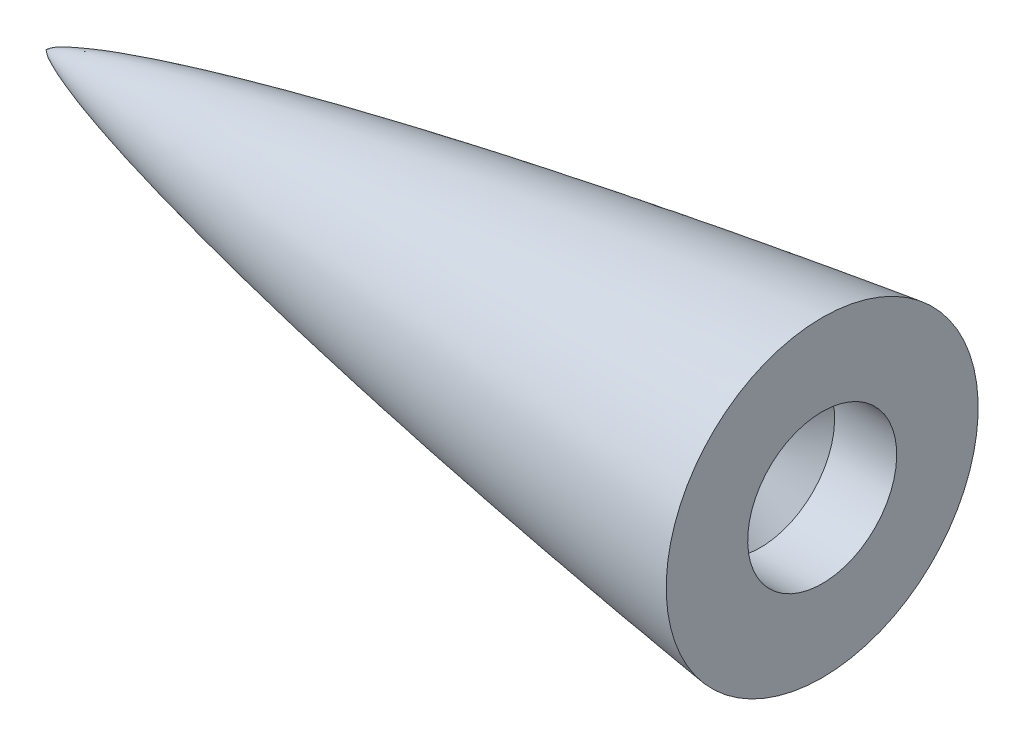
SolidWorks part; units mm, degrees
material "ABS"
ref_plane "Front Plane" through (0, 0, 0) normal (0, 0, 1) x (1, 0, 0)
ref_plane "Top Plane" through (0, 0, 0) normal (0, 1, 0) x (1, 0, 0)
ref_plane "Right Plane" through (0, 0, 0) normal (1, 0, 0) x (0, 0, -1)
curve "Curve1"
  spline degree 3 poles (0, 0, 0) (0.3238, 0.2558, 0) (0.9402, 0.7427, 0) (1.9959, 1.205, 0) (2.9891, 1.6586, 0) (3.9977, 2.0398, 0) (4.9964, 2.4132, 0) (5.9986, 2.7607, 0) (6.9987, 3.1004, 0) (7.9965, 3.4344, 0) (9.0008, 3.7373, 0) (9.9965, 4.055, 0) (11.0004, 4.3386, 0) (12, 4.6299, 0) (12.9986, 4.9215, 0) (13.9986, 5.202, 0) (15.0003, 5.4688, 0) (15.9984, 5.7426, 0) (17.0001, 5.9995, 0) (18.0001, 6.2594, 0) (18.9985, 6.5227, 0) (20.0004, 6.7686, 0) (20.9985, 7.0227, 0) (22.0002, 7.2591, 0) (22.9999, 7.5005, 0) (24.0003, 7.7389, 0) (24.9983, 7.9838, 0) (26.0019, 8.205, 0) (26.9969, 8.4568, 0) (28.0017, 8.6659, 0) (28.9999, 8.9005, 0) (29.9988, 9.1322, 0) (31.0001, 9.3496, 0) (32.0002, 9.5692, 0) (32.9985, 9.7935, 0) (34.0016, 9.9959, 0) (34.9985, 10.2236, 0) (36.0002, 10.4289, 0) (36.9999, 10.6405, 0) (38.0002, 10.8489, 0) (38.9986, 11.0636, 0) (40.0015, 11.2559, 0) (40.9986, 11.4736, 0) (42.0002, 11.6689, 0) (42.9999, 11.8705, 0) (44.0002, 12.0689, 0) (44.9986, 12.2737, 0) (46.0015, 12.4556, 0) (46.9985, 12.6646, 0) (48.0015, 12.8456, 0) (48.9986, 13.0537, 0) (50.0002, 13.2389, 0) (50.9999, 13.4305, 0) (52.0002, 13.619, 0) (52.9988, 13.8134, 0) (54.0012, 13.9868, 0) (55, 14.1802, 0) (55.9989, 14.3724, 0) (57.0001, 14.5493, 0) (58, 14.7302, 0) (59, 14.9099, 0) (60, 15.09, 0) (61, 15.2699, 0) (62, 15.4503, 0) (63.0002, 15.629, 0) (63.9988, 15.8137, 0) (65.0013, 15.9758, 0) (65.9988, 16.1637, 0) (67.0002, 16.329, 0) (68, 16.5003, 0) (69, 16.6699, 0) (70, 16.84, 0) (71, 17.01, 0) (72, 17.1799, 0) (73, 17.3503, 0) (74.0002, 17.519, 0) (74.9988, 17.6937, 0) (76.0012, 17.8458, 0) (76.9989, 18.0234, 0) (78, 18.1799, 0) (79.0011, 18.3368, 0) (79.9989, 18.5134, 0) (81.0002, 18.6691, 0) (82, 18.8303, 0) (83, 18.9899, 0) (84, 19.1503, 0) (85.0001, 19.3091, 0) (85.999, 19.4734, 0) (87.001, 19.6168, 0) (88, 19.78, 0) (88.999, 19.9434, 0) (90.0012, 20.0859, 0) (90.999, 20.2534, 0) (92, 20.4, 0) (93.001, 20.5468, 0) (93.999, 20.7134, 0) (95.0001, 20.8591, 0) (96, 21.0103, 0) (97, 21.1599, 0) (98, 21.3103, 0) (99.0001, 21.4591, 0) (99.999, 21.6134, 0) (101.001, 21.7468, 0) (102, 21.8999, 0) (102.999, 22.0535, 0) (104.0011, 22.1855, 0) (104.9988, 22.3446, 0) (106.0011, 22.4755, 0) (106.999, 22.6335, 0) (108, 22.7699, 0) (109.001, 22.9068, 0) (109.999, 23.0634, 0) (111.0001, 23.1991, 0) (112, 23.3402, 0) (113, 23.48, 0) (114, 23.62, 0) (115, 23.7602, 0) (116.0001, 23.8991, 0) (116.9991, 24.0435, 0) (118.0009, 24.1667, 0) (119, 24.3099, 0) (119.9991, 24.4535, 0) (121.0011, 24.5755, 0) (121.9989, 24.7247, 0) (123.0011, 24.8455, 0) (123.9991, 24.9935, 0) (125, 25.1199, 0) (126.0009, 25.2467, 0) (126.9991, 25.3935, 0) (128.0001, 25.5191, 0) (129, 25.6503, 0) (130, 25.7799, 0) (131, 25.91, 0) (132, 26.0399, 0) (133, 26.1703, 0) (134.0001, 26.2991, 0) (134.9991, 26.4335, 0) (136.0008, 26.5467, 0) (137, 26.6799, 0) (137.9991, 26.8136, 0) (139.001, 26.9255, 0) (139.999, 27.0647, 0) (141.001, 27.1755, 0) (141.9991, 27.3136, 0) (143, 27.4299, 0) (144.0008, 27.5467, 0) (144.9991, 27.6835, 0) (146.0001, 27.7991, 0) (147, 27.9203, 0) (148, 28.0399, 0) (149, 28.16, 0) (150, 28.28, 0) (151, 28.4, 0) (152, 28.52, 0) (153, 28.6399, 0) (154, 28.7603, 0) (155.0001, 28.879, 0) (155.9992, 29.0038, 0) (157.0009, 29.1054, 0) (157.9991, 29.2348, 0) (159.0009, 29.3351, 0) (159.9991, 29.4649, 0) (161.0009, 29.5651, 0) (161.9991, 29.6948, 0) (163.0009, 29.7954, 0) (163.9992, 29.9238, 0) (165.0001, 30.029, 0) (166, 30.1403, 0) (167, 30.2499, 0) (168, 30.36, 0) (169, 30.47, 0) (170, 30.58, 0) (171, 30.69, 0) (172, 30.8, 0) (173, 30.9099, 0) (174, 31.0203, 0) (175.0001, 31.129, 0) (175.9992, 31.2439, 0) (177.0008, 31.3354, 0) (177.9991, 31.4548, 0) (179.0009, 31.5451, 0) (179.9991, 31.6649, 0) (181.0009, 31.7551, 0) (181.9991, 31.8748, 0) (183.0008, 31.9654, 0) (183.9992, 32.0838, 0) (185.0001, 32.179, 0) (186, 32.28, 0) (186.9999, 32.3809, 0) (188.0007, 32.4765, 0) (188.9993, 32.5935, 0) (190.0001, 32.6893, 0) (191.0001, 32.7893, 0) (191.9993, 32.8935, 0) (193.0007, 32.9764, 0) (193.9999, 33.0812, 0) (195.0001, 33.1788, 0) (195.9993, 33.2836, 0) (197.0006, 33.3667, 0) (198, 33.4699, 0) (198.9993, 33.5736, 0) (200.0007, 33.6554, 0) (200.9992, 33.7648, 0) (202.0008, 33.8454, 0) (202.9993, 33.9539, 0) (204.0001, 34.0387, 0) (204.9999, 34.1313, 0) (206.0007, 34.2163, 0) (206.9993, 34.3236, 0) (208.0001, 34.409, 0) (209, 34.5003, 0) (210, 34.5899, 0) (211, 34.6803, 0) (212.0001, 34.769, 0) (212.9994, 34.8635, 0) (214.0006, 34.9366, 0) (215, 35.03, 0) (215.9994, 35.1233, 0) (217.0006, 35.1967, 0) (218, 35.2899, 0) (218.9994, 35.3835, 0) (220.0006, 35.4558, 0) (220.9994, 35.5535, 0) (222, 35.6299, 0) (223.0006, 35.7067, 0) (223.9994, 35.8035, 0) (225.0001, 35.879, 0) (226, 35.9603, 0) (227, 36.0399, 0) (228, 36.12, 0) (229, 36.2, 0) (230, 36.2799, 0) (231, 36.3603, 0) (232.0001, 36.439, 0) (232.9995, 36.5235, 0) (234.0005, 36.5867, 0) (235, 36.6699, 0) (235.9995, 36.7535, 0) (237.0006, 36.8157, 0) (237.9995, 36.9035, 0) (239, 36.9699, 0) (240.0005, 37.0367, 0) (240.9995, 37.1235, 0) (242.0001, 37.189, 0) (243, 37.2603, 0) (244, 37.3299, 0) (245, 37.4, 0) (246, 37.47, 0) (247, 37.5399, 0) (248, 37.6103, 0) (249.0001, 37.6789, 0) (249.9995, 37.7539, 0) (251.0005, 37.8053, 0) (251.9995, 37.8849, 0) (253.0005, 37.9351, 0) (253.9995, 38.0149, 0) (255.0005, 38.0653, 0) (255.9995, 38.1439, 0) (257.0001, 38.1989, 0) (258, 38.2603, 0) (259, 38.3199, 0) (260, 38.38, 0) (261, 38.4399, 0) (262, 38.5003, 0) (263.0001, 38.5589, 0) (263.9996, 38.6239, 0) (265.0004, 38.6653, 0) (265.9995, 38.7349, 0) (267.0005, 38.7751, 0) (267.9995, 38.8449, 0) (269.0004, 38.8853, 0) (269.9996, 38.9539, 0) (271.0001, 38.999, 0) (272, 39.0502, 0) (273, 39.1002, 0) (274, 39.1491, 0) (274.9997, 39.2036, 0) (276.0003, 39.2365, 0) (277, 39.2903, 0) (277.9997, 39.3424, 0) (279, 39.3803, 0) (280.0003, 39.4166, 0) (280.9997, 39.4735, 0) (282, 39.5093, 0) (283, 39.5493, 0) (283.9998, 39.5935, 0) (285.0002, 39.6166, 0) (286, 39.6602, 0) (286.9998, 39.7026, 0) (288, 39.7293, 0) (289, 39.7602, 0) (290, 39.7899, 0) (291, 39.8203, 0) (292, 39.849, 0) (292.9998, 39.8839, 0) (294.0002, 39.8955, 0) (294.9998, 39.9341, 0) (296, 39.9482, 0) (296.9999, 39.9732, 0) (298, 39.9792, 0) (299, 39.9902, 0) (299.6667, 39.9967, 0) (300, 40, 0) knots 0 0 0 0 0.004059 0.007728 0.011327 0.014863 0.018375 0.021865 0.025345 0.028814 0.032263 0.035712 0.039142 0.042572 0.046002 0.049423 0.052835 0.056247 0.059651 0.063054 0.066458 0.069854 0.07325 0.076637 0.080025 0.083413 0.086801 0.090181 0.093569 0.096942 0.100322 0.103702 0.107075 0.110448 0.113821 0.117187 0.120561 0.123927 0.127293 0.130659 0.134025 0.137384 0.140751 0.14411 0.147469 0.150829 0.154188 0.157542 0.160901 0.164254 0.167614 0.170967 0.17432 0.177673 0.181027 0.184374 0.187727 0.19108 0.194427 0.197774 0.201122 0.204469 0.207816 0.211163 0.21451 0.217858 0.221199 0.224546 0.227888 0.231229 0.234571 0.237912 0.241254 0.244595 0.247937 0.251278 0.25462 0.257956 0.261298 0.264634 0.26797 0.271311 0.274648 0.277984 0.28132 0.284656 0.287992 0.291328 0.294659 0.297995 0.301332 0.304663 0.307999 0.31133 0.314661 0.317997 0.321328 0.324659 0.327991 0.331322 0.334653 0.337984 0.34131 0.344641 0.347972 0.351299 0.35463 0.357956 0.361287 0.364614 0.36794 0.371271 0.374598 0.377924 0.38125 0.384577 0.387903 0.391229 0.394556 0.397878 0.401204 0.404531 0.407853 0.411179 0.414501 0.417827 0.421149 0.424471 0.427798 0.43112 0.434442 0.437763 0.441085 0.444407 0.447729 0.451051 0.454373 0.457691 0.461013 0.464335 0.467653 0.470975 0.474293 0.477615 0.480933 0.484251 0.487573 0.49089 0.494208 0.497526 0.500844 0.504162 0.50748 0.510798 0.514116 0.517434 0.520751 0.524069 0.527383 0.530701 0.534015 0.537333 0.540647 0.543965 0.547279 0.550597 0.553911 0.557226 0.56054 0.563854 0.567168 0.570482 0.573796 0.57711 0.580424 0.583738 0.587053 0.590367 0.593677 0.596991 0.600302 0.603616 0.606927 0.610241 0.613552 0.616866 0.620177 0.623487 0.626798 0.630109 0.633423 0.636733 0.640044 0.643355 0.646662 0.649973 0.653284 0.656594 0.659902 0.663213 0.666523 0.669831 0.673142 0.676449 0.67976 0.683067 0.686375 0.689682 0.692993 0.696301 0.699608 0.702916 0.706223 0.709531 0.712838 0.716143 0.719451 0.722758 0.726063 0.729371 0.732678 0.735983 0.739291 0.742595 0.7459 0.749208 0.752513 0.755817 0.759122 0.762427 0.765732 0.769036 0.772341 0.775646 0.778951 0.782253 0.785558 0.788863 0.792165 0.79547 0.798772 0.802074 0.805379 0.808681 0.811984 0.815286 0.818588 0.821891 0.825193 0.828495 0.831797 0.8351 0.8384 0.841702 0.845002 0.848305 0.851605 0.854907 0.858207 0.861508 0.864808 0.868108 0.871408 0.874708 0.878008 0.881309 0.884607 0.887907 0.891206 0.894506 0.897804 0.901104 0.904403 0.907701 0.910999 0.914298 0.917596 0.920893 0.924191 0.92749 0.930787 0.934083 0.937382 0.940679 0.943976 0.947272 0.950568 0.953865 0.957162 0.960458 0.963753 0.967049 0.970345 0.973641 0.976936 0.980231 0.983527 0.986822 0.990117 0.993411 0.996706 1 1 1 1
sketch "Sketch1" plane through (0, 0, 0) normal (0, 0, 1) x (1, 0, 0)
  line L0 (125, 25.12) -> (125, 3.175)
  line L1 (21.825, 0) -> (0, 0)
  line L2 (1366, 0) -> (125, 0) construction
  line L3 (125, 3.175) -> (25, 3.175)
  line L4 (25, 3.175) -> (21.825, 0)
  line L5 (21.825, 0) -> (-59.4496, 0) construction
  line L6 (125, 12) -> (115, 12)
  line L7 (115, 12) -> (106.175, 3.175)
  spline S0 degree 3 poles (-1070.3353, 1688.9679) (10.2744, -68.4827) (-11.5783, -4.7393) (1.9959, 1.205) (2.9891, 1.6586) (3.9977, 2.0398) (4.9964, 2.4132) (5.9986, 2.7607) (6.9987, 3.1004) (7.9965, 3.4344) (9.0008, 3.7373) (9.9965, 4.055) (11.0004, 4.3386) (12, 4.6299) (12.9986, 4.9215) (13.9986, 5.202) (15.0003, 5.4688) (15.9984, 5.7426) (17.0001, 5.9995) (18.0001, 6.2594) (18.9985, 6.5227) (20.0004, 6.7686) (20.9985, 7.0227) (22.0002, 7.2591) (22.9999, 7.5005) (24.0003, 7.7389) (24.9983, 7.9838) (26.0019, 8.205) (26.9969, 8.4568) (28.0017, 8.6659) (28.9999, 8.9005) (29.9988, 9.1322) (31.0001, 9.3496) (32.0002, 9.5692) (32.9985, 9.7935) (34.0016, 9.9959) (34.9985, 10.2236) (36.0002, 10.4289) (36.9999, 10.6405) (38.0002, 10.8489) (38.9986, 11.0636) (40.0015, 11.2559) (40.9986, 11.4736) (42.0002, 11.6689) (42.9999, 11.8705) (44.0002, 12.0689) (44.9986, 12.2737) (46.0015, 12.4556) (46.9985, 12.6646) (48.0015, 12.8456) (48.9986, 13.0537) (50.0002, 13.2389) (50.9999, 13.4305) (52.0002, 13.619) (52.9988, 13.8134) (54.0012, 13.9868) (55, 14.1802) (55.9989, 14.3724) (57.0001, 14.5493) (58, 14.7302) (59, 14.9099) (60, 15.09) (61, 15.2699) (62, 15.4503) (63.0002, 15.629) (63.9988, 15.8137) (65.0013, 15.9758) (65.9988, 16.1637) (67.0002, 16.329) (68, 16.5003) (69, 16.6699) (70, 16.84) (71, 17.01) (72, 17.1799) (73, 17.3503) (74.0002, 17.519) (74.9988, 17.6937) (76.0012, 17.8458) (76.9989, 18.0234) (78, 18.1799) (79.0011, 18.3368) (79.9989, 18.5134) (81.0002, 18.6691) (82, 18.8303) (83, 18.9899) (84, 19.1503) (85.0001, 19.3091) (85.999, 19.4734) (87.001, 19.6168) (88, 19.78) (88.999, 19.9434) (90.0012, 20.0859) (90.999, 20.2534) (92, 20.4) (93.001, 20.5468) (93.999, 20.7134) (95.0001, 20.8591) (96, 21.0103) (97, 21.1599) (98, 21.3103) (99.0001, 21.4591) (99.999, 21.6134) (101.001, 21.7468) (102, 21.8999) (102.999, 22.0535) (104.0011, 22.1855) (104.9988, 22.3446) (106.0011, 22.4755) (106.999, 22.6335) (108, 22.7699) (109.001, 22.9068) (109.999, 23.0634) (111.0001, 23.1991) (112, 23.3402) (113, 23.48) (114, 23.62) (115, 23.7602) (116.0001, 23.8991) (116.9991, 24.0435) (118.0009, 24.1667) (119, 24.3099) (119.9991, 24.4535) (121.0011, 24.5755) (121.9989, 24.7247) (123.0011, 24.8455) (123.9991, 24.9935) (125, 25.1199) (126.0009, 25.2467) (126.9991, 25.3935) (128.0001, 25.5191) (129, 25.6503) (130, 25.7799) (131, 25.91) (132, 26.0399) (133, 26.1703) (134.0001, 26.2991) (134.9991, 26.4335) (136.0008, 26.5467) (137, 26.6799) (137.9991, 26.8136) (139.001, 26.9255) (139.999, 27.0647) (141.001, 27.1755) (141.9991, 27.3136) (143, 27.4299) (144.0008, 27.5467) (144.9991, 27.6835) (146.0001, 27.7991) (147, 27.9203) (148, 28.0399) (149, 28.16) (150, 28.28) (151, 28.4) (152, 28.52) (153, 28.6399) (154, 28.7603) (155.0001, 28.879) (155.9992, 29.0038) (157.0009, 29.1054) (157.9991, 29.2348) (159.0009, 29.3351) (159.9991, 29.4649) (161.0009, 29.5651) (161.9991, 29.6948) (163.0009, 29.7954) (163.9992, 29.9238) (165.0001, 30.029) (166, 30.1403) (167, 30.2499) (168, 30.36) (169, 30.47) (170, 30.58) (171, 30.69) (172, 30.8) (173, 30.9099) (174, 31.0203) (175.0001, 31.129) (175.9992, 31.2439) (177.0008, 31.3354) (177.9991, 31.4548) (179.0009, 31.5451) (179.9991, 31.6649) (181.0009, 31.7551) (181.9991, 31.8748) (183.0008, 31.9654) (183.9992, 32.0838) (185.0001, 32.179) (186, 32.28) (186.9999, 32.3809) (188.0007, 32.4765) (188.9993, 32.5935) (190.0001, 32.6893) (191.0001, 32.7893) (191.9993, 32.8935) (193.0007, 32.9764) (193.9999, 33.0812) (195.0001, 33.1788) (195.9993, 33.2836) (197.0006, 33.3667) (198, 33.4699) (198.9993, 33.5736) (200.0007, 33.6554) (200.9992, 33.7648) (202.0008, 33.8454) (202.9993, 33.9539) (204.0001, 34.0387) (204.9999, 34.1313) (206.0007, 34.2163) (206.9993, 34.3236) (208.0001, 34.409) (209, 34.5003) (210, 34.5899) (211, 34.6803) (212.0001, 34.769) (212.9994, 34.8635) (214.0006, 34.9366) (215, 35.03) (215.9994, 35.1233) (217.0006, 35.1967) (218, 35.2899) (218.9994, 35.3835) (220.0006, 35.4558) (220.9994, 35.5535) (222, 35.6299) (223.0006, 35.7067) (223.9994, 35.8035) (225.0001, 35.879) (226, 35.9603) (227, 36.0399) (228, 36.12) (229, 36.2) (230, 36.2799) (231, 36.3603) (232.0001, 36.439) (232.9995, 36.5235) (234.0005, 36.5867) (235, 36.6699) (235.9995, 36.7535) (237.0006, 36.8157) (237.9995, 36.9035) (239, 36.9699) (240.0005, 37.0367) (240.9995, 37.1235) (242.0001, 37.189) (243, 37.2603) (244, 37.3299) (245, 37.4) (246, 37.47) (247, 37.5399) (248, 37.6103) (249.0001, 37.6789) (249.9995, 37.7539) (251.0005, 37.8053) (251.9995, 37.8849) (253.0005, 37.9351) (253.9995, 38.0149) (255.0005, 38.0653) (255.9995, 38.1439) (257.0001, 38.1989) (258, 38.2603) (259, 38.3199) (260, 38.38) (261, 38.4399) (262, 38.5003) (263.0001, 38.5589) (263.9996, 38.6239) (265.0004, 38.6653) (265.9995, 38.7349) (267.0005, 38.7751) (267.9995, 38.8449) (269.0004, 38.8853) (269.9996, 38.9539) (271.0001, 38.999) (272, 39.0502) (273, 39.1002) (274, 39.1491) (274.9997, 39.2036) (276.0003, 39.2365) (277, 39.2903) (277.9997, 39.3424) (279, 39.3803) (280.0003, 39.4166) (280.9997, 39.4735) (282, 39.5093) (283, 39.5493) (283.9998, 39.5935) (285.0002, 39.6166) (286, 39.6602) (286.9998, 39.7026) (288, 39.7293) (289, 39.7602) (290, 39.7899) (291, 39.8203) (292, 39.849) (292.9998, 39.8839) (294.0002, 39.8955) (294.9998, 39.9341) (296, 39.9482) (296.9999, 39.9732) (298, 39.9792) (369.4003, 40.7684) (440.6193, 31.9722) (479.6754, 2027.9914) knots -0.134313 -0.134313 -0.134313 -0.134313 0.004059 0.007728 0.011327 0.014863 0.018375 0.021865 0.025345 0.028814 0.032263 0.035712 0.039142 0.042572 0.046002 0.049423 0.052835 0.056247 0.059651 0.063054 0.066458 0.069854 0.07325 0.076637 0.080025 0.083413 0.086801 0.090181 0.093569 0.096942 0.100322 0.103702 0.107075 0.110448 0.113821 0.117187 0.120561 0.123927 0.127293 0.130659 0.134025 0.137384 0.140751 0.14411 0.147469 0.150829 0.154188 0.157542 0.160901 0.164254 0.167614 0.170967 0.17432 0.177673 0.181027 0.184374 0.187727 0.19108 0.194427 0.197774 0.201122 0.204469 0.207816 0.211163 0.21451 0.217858 0.221199 0.224546 0.227888 0.231229 0.234571 0.237912 0.241254 0.244595 0.247937 0.251278 0.25462 0.257956 0.261298 0.264634 0.26797 0.271311 0.274648 0.277984 0.28132 0.284656 0.287992 0.291328 0.294659 0.297995 0.301332 0.304663 0.307999 0.31133 0.314661 0.317997 0.321328 0.324659 0.327991 0.331322 0.334653 0.337984 0.34131 0.344641 0.347972 0.351299 0.35463 0.357956 0.361287 0.364614 0.36794 0.371271 0.374598 0.377924 0.38125 0.384577 0.387903 0.391229 0.394556 0.397878 0.401204 0.404531 0.407853 0.411179 0.414501 0.417827 0.421149 0.424471 0.427798 0.43112 0.434442 0.437763 0.441085 0.444407 0.447729 0.451051 0.454373 0.457691 0.461013 0.464335 0.467653 0.470975 0.474293 0.477615 0.480933 0.484251 0.487573 0.49089 0.494208 0.497526 0.500844 0.504162 0.50748 0.510798 0.514116 0.517434 0.520751 0.524069 0.527383 0.530701 0.534015 0.537333 0.540647 0.543965 0.547279 0.550597 0.553911 0.557226 0.56054 0.563854 0.567168 0.570482 0.573796 0.57711 0.580424 0.583738 0.587053 0.590367 0.593677 0.596991 0.600302 0.603616 0.606927 0.610241 0.613552 0.616866 0.620177 0.623487 0.626798 0.630109 0.633423 0.636733 0.640044 0.643355 0.646662 0.649973 0.653284 0.656594 0.659902 0.663213 0.666523 0.669831 0.673142 0.676449 0.67976 0.683067 0.686375 0.689682 0.692993 0.696301 0.699608 0.702916 0.706223 0.709531 0.712838 0.716143 0.719451 0.722758 0.726063 0.729371 0.732678 0.735983 0.739291 0.742595 0.7459 0.749208 0.752513 0.755817 0.759122 0.762427 0.765732 0.769036 0.772341 0.775646 0.778951 0.782253 0.785558 0.788863 0.792165 0.79547 0.798772 0.802074 0.805379 0.808681 0.811984 0.815286 0.818588 0.821891 0.825193 0.828495 0.831797 0.8351 0.8384 0.841702 0.845002 0.848305 0.851605 0.854907 0.858207 0.861508 0.864808 0.868108 0.871408 0.874708 0.878008 0.881309 0.884607 0.887907 0.891206 0.894506 0.897804 0.901104 0.904403 0.907701 0.910999 0.914298 0.917596 0.920893 0.924191 0.92749 0.930787 0.934083 0.937382 0.940679 0.943976 0.947272 0.950568 0.953865 0.957162 0.960458 0.963753 0.967049 0.970345 0.973641 0.976936 0.980231 0.983527 0.986822 0.990117 0.993411 0.996706 1.695794 1.695794 1.695794 1.695794 only from (0, 0) to (300, 40) construction
  spline S1 degree 3 poles (0, 0) (0.3238, 0.2558) (0.9402, 0.7427) (1.9959, 1.205) (2.9891, 1.6586) (3.9977, 2.0398) (4.9964, 2.4132) (5.9986, 2.7607) (6.9987, 3.1004) (7.9965, 3.4344) (9.0008, 3.7373) (9.9965, 4.055) (11.0004, 4.3386) (12, 4.6299) (12.9986, 4.9215) (13.9986, 5.202) (15.0003, 5.4688) (15.9984, 5.7426) (17.0001, 5.9995) (18.0001, 6.2594) (18.9985, 6.5227) (20.0004, 6.7686) (20.9985, 7.0227) (22.0002, 7.2591) (22.9999, 7.5005) (24.0003, 7.7389) (24.9983, 7.9838) (26.0019, 8.205) (26.9969, 8.4568) (28.0017, 8.6659) (28.9999, 8.9005) (29.9988, 9.1322) (31.0001, 9.3496) (32.0002, 9.5692) (32.9985, 9.7935) (34.0016, 9.9959) (34.9985, 10.2236) (36.0002, 10.4289) (36.9999, 10.6405) (38.0002, 10.8489) (38.9986, 11.0636) (40.0015, 11.2559) (40.9986, 11.4736) (42.0002, 11.6689) (42.9999, 11.8705) (44.0002, 12.0689) (44.9986, 12.2737) (46.0015, 12.4556) (46.9985, 12.6646) (48.0015, 12.8456) (48.9986, 13.0537) (50.0002, 13.2389) (50.9999, 13.4305) (52.0002, 13.619) (52.9988, 13.8134) (54.0012, 13.9868) (55, 14.1802) (55.9989, 14.3724) (57.0001, 14.5493) (58, 14.7302) (59, 14.9099) (60, 15.09) (61, 15.2699) (62, 15.4503) (63.0002, 15.629) (63.9988, 15.8137) (65.0013, 15.9758) (65.9988, 16.1637) (67.0002, 16.329) (68, 16.5003) (69, 16.6699) (70, 16.84) (71, 17.01) (72, 17.1799) (73, 17.3503) (74.0002, 17.519) (74.9988, 17.6937) (76.0012, 17.8458) (76.9989, 18.0234) (78, 18.1799) (79.0011, 18.3368) (79.9989, 18.5134) (81.0002, 18.6691) (82, 18.8303) (83, 18.9899) (84, 19.1503) (85.0001, 19.3091) (85.999, 19.4734) (87.001, 19.6168) (88, 19.78) (88.999, 19.9434) (90.0012, 20.0859) (90.999, 20.2534) (92, 20.4) (93.001, 20.5468) (93.999, 20.7134) (95.0001, 20.8591) (96, 21.0103) (97, 21.1599) (98, 21.3103) (99.0001, 21.4591) (99.999, 21.6134) (101.001, 21.7468) (102, 21.8999) (102.999, 22.0535) (104.0011, 22.1855) (104.9988, 22.3446) (106.0011, 22.4755) (106.999, 22.6335) (108, 22.7699) (109.001, 22.9068) (109.999, 23.0634) (111.0001, 23.1991) (112, 23.3402) (113, 23.48) (114, 23.62) (115, 23.7602) (116.0001, 23.8991) (116.9991, 24.0435) (118.0009, 24.1667) (119, 24.3099) (119.9991, 24.4535) (121.0011, 24.5755) (121.9989, 24.7247) (123.0011, 24.8455) (123.9991, 24.9935) (125, 25.1199) (126.0009, 25.2467) (126.9991, 25.3935) (128.0001, 25.5191) (129, 25.6503) (130, 25.7799) (131, 25.91) (132, 26.0399) (133, 26.1703) (134.0001, 26.2991) (134.9991, 26.4335) (136.0008, 26.5467) (137, 26.6799) (137.9991, 26.8136) (139.001, 26.9255) (139.999, 27.0647) (141.001, 27.1755) (141.9991, 27.3136) (143, 27.4299) (144.0008, 27.5467) (144.9991, 27.6835) (146.0001, 27.7991) (147, 27.9203) (148, 28.0399) (149, 28.16) (150, 28.28) (151, 28.4) (152, 28.52) (153, 28.6399) (154, 28.7603) (155.0001, 28.879) (155.9992, 29.0038) (157.0009, 29.1054) (157.9991, 29.2348) (159.0009, 29.3351) (159.9991, 29.4649) (161.0009, 29.5651) (161.9991, 29.6948) (163.0009, 29.7954) (163.9992, 29.9238) (165.0001, 30.029) (166, 30.1403) (167, 30.2499) (168, 30.36) (169, 30.47) (170, 30.58) (171, 30.69) (172, 30.8) (173, 30.9099) (174, 31.0203) (175.0001, 31.129) (175.9992, 31.2439) (177.0008, 31.3354) (177.9991, 31.4548) (179.0009, 31.5451) (179.9991, 31.6649) (181.0009, 31.7551) (181.9991, 31.8748) (183.0008, 31.9654) (183.9992, 32.0838) (185.0001, 32.179) (186, 32.28) (186.9999, 32.3809) (188.0007, 32.4765) (188.9993, 32.5935) (190.0001, 32.6893) (191.0001, 32.7893) (191.9993, 32.8935) (193.0007, 32.9764) (193.9999, 33.0812) (195.0001, 33.1788) (195.9993, 33.2836) (197.0006, 33.3667) (198, 33.4699) (198.9993, 33.5736) (200.0007, 33.6554) (200.9992, 33.7648) (202.0008, 33.8454) (202.9993, 33.9539) (204.0001, 34.0387) (204.9999, 34.1313) (206.0007, 34.2163) (206.9993, 34.3236) (208.0001, 34.409) (209, 34.5003) (210, 34.5899) (211, 34.6803) (212.0001, 34.769) (212.9994, 34.8635) (214.0006, 34.9366) (215, 35.03) (215.9994, 35.1233) (217.0006, 35.1967) (218, 35.2899) (218.9994, 35.3835) (220.0006, 35.4558) (220.9994, 35.5535) (222, 35.6299) (223.0006, 35.7067) (223.9994, 35.8035) (225.0001, 35.879) (226, 35.9603) (227, 36.0399) (228, 36.12) (229, 36.2) (230, 36.2799) (231, 36.3603) (232.0001, 36.439) (232.9995, 36.5235) (234.0005, 36.5867) (235, 36.6699) (235.9995, 36.7535) (237.0006, 36.8157) (237.9995, 36.9035) (239, 36.9699) (240.0005, 37.0367) (240.9995, 37.1235) (242.0001, 37.189) (243, 37.2603) (244, 37.3299) (245, 37.4) (246, 37.47) (247, 37.5399) (248, 37.6103) (249.0001, 37.6789) (249.9995, 37.7539) (251.0005, 37.8053) (251.9995, 37.8849) (253.0005, 37.9351) (253.9995, 38.0149) (255.0005, 38.0653) (255.9995, 38.1439) (257.0001, 38.1989) (258, 38.2603) (259, 38.3199) (260, 38.38) (261, 38.4399) (262, 38.5003) (263.0001, 38.5589) (263.9996, 38.6239) (265.0004, 38.6653) (265.9995, 38.7349) (267.0005, 38.7751) (267.9995, 38.8449) (269.0004, 38.8853) (269.9996, 38.9539) (271.0001, 38.999) (272, 39.0502) (273, 39.1002) (274, 39.1491) (274.9997, 39.2036) (276.0003, 39.2365) (277, 39.2903) (277.9997, 39.3424) (279, 39.3803) (280.0003, 39.4166) (280.9997, 39.4735) (282, 39.5093) (283, 39.5493) (283.9998, 39.5935) (285.0002, 39.6166) (286, 39.6602) (286.9998, 39.7026) (288, 39.7293) (289, 39.7602) (290, 39.7899) (291, 39.8203) (292, 39.849) (292.9998, 39.8839) (294.0002, 39.8955) (294.9998, 39.9341) (296, 39.9482) (296.9999, 39.9732) (298, 39.9792) (299, 39.9902) (299.6667, 39.9967) (300, 40) knots 0 0 0 0 0.004059 0.007728 0.011327 0.014863 0.018375 0.021865 0.025345 0.028814 0.032263 0.035712 0.039142 0.042572 0.046002 0.049423 0.052835 0.056247 0.059651 0.063054 0.066458 0.069854 0.07325 0.076637 0.080025 0.083413 0.086801 0.090181 0.093569 0.096942 0.100322 0.103702 0.107075 0.110448 0.113821 0.117187 0.120561 0.123927 0.127293 0.130659 0.134025 0.137384 0.140751 0.14411 0.147469 0.150829 0.154188 0.157542 0.160901 0.164254 0.167614 0.170967 0.17432 0.177673 0.181027 0.184374 0.187727 0.19108 0.194427 0.197774 0.201122 0.204469 0.207816 0.211163 0.21451 0.217858 0.221199 0.224546 0.227888 0.231229 0.234571 0.237912 0.241254 0.244595 0.247937 0.251278 0.25462 0.257956 0.261298 0.264634 0.26797 0.271311 0.274648 0.277984 0.28132 0.284656 0.287992 0.291328 0.294659 0.297995 0.301332 0.304663 0.307999 0.31133 0.314661 0.317997 0.321328 0.324659 0.327991 0.331322 0.334653 0.337984 0.34131 0.344641 0.347972 0.351299 0.35463 0.357956 0.361287 0.364614 0.36794 0.371271 0.374598 0.377924 0.38125 0.384577 0.387903 0.391229 0.394556 0.397878 0.401204 0.404531 0.407853 0.411179 0.414501 0.417827 0.421149 0.424471 0.427798 0.43112 0.434442 0.437763 0.441085 0.444407 0.447729 0.451051 0.454373 0.457691 0.461013 0.464335 0.467653 0.470975 0.474293 0.477615 0.480933 0.484251 0.487573 0.49089 0.494208 0.497526 0.500844 0.504162 0.50748 0.510798 0.514116 0.517434 0.520751 0.524069 0.527383 0.530701 0.534015 0.537333 0.540647 0.543965 0.547279 0.550597 0.553911 0.557226 0.56054 0.563854 0.567168 0.570482 0.573796 0.57711 0.580424 0.583738 0.587053 0.590367 0.593677 0.596991 0.600302 0.603616 0.606927 0.610241 0.613552 0.616866 0.620177 0.623487 0.626798 0.630109 0.633423 0.636733 0.640044 0.643355 0.646662 0.649973 0.653284 0.656594 0.659902 0.663213 0.666523 0.669831 0.673142 0.676449 0.67976 0.683067 0.686375 0.689682 0.692993 0.696301 0.699608 0.702916 0.706223 0.709531 0.712838 0.716143 0.719451 0.722758 0.726063 0.729371 0.732678 0.735983 0.739291 0.742595 0.7459 0.749208 0.752513 0.755817 0.759122 0.762427 0.765732 0.769036 0.772341 0.775646 0.778951 0.782253 0.785558 0.788863 0.792165 0.79547 0.798772 0.802074 0.805379 0.808681 0.811984 0.815286 0.818588 0.821891 0.825193 0.828495 0.831797 0.8351 0.8384 0.841702 0.845002 0.848305 0.851605 0.854907 0.858207 0.861508 0.864808 0.868108 0.871408 0.874708 0.878008 0.881309 0.884607 0.887907 0.891206 0.894506 0.897804 0.901104 0.904403 0.907701 0.910999 0.914298 0.917596 0.920893 0.924191 0.92749 0.930787 0.934083 0.937382 0.940679 0.943976 0.947272 0.950568 0.953865 0.957162 0.960458 0.963753 0.967049 0.970345 0.973641 0.976936 0.980231 0.983527 0.986822 0.990117 0.993411 0.996706 1 1 1 1
  dimension "D1" = 175
  dimension "D2" = 135
  dimension "D3" = 100
  dimension "D4" = 3.175
  dimension "D5" = 135
  dimension "D6" = 12
  dimension "D7" = 10
revolve "Revolve1" add sketch "Sketch1" angle 360 about L2 region at (76.363, 10.8926, 0)
